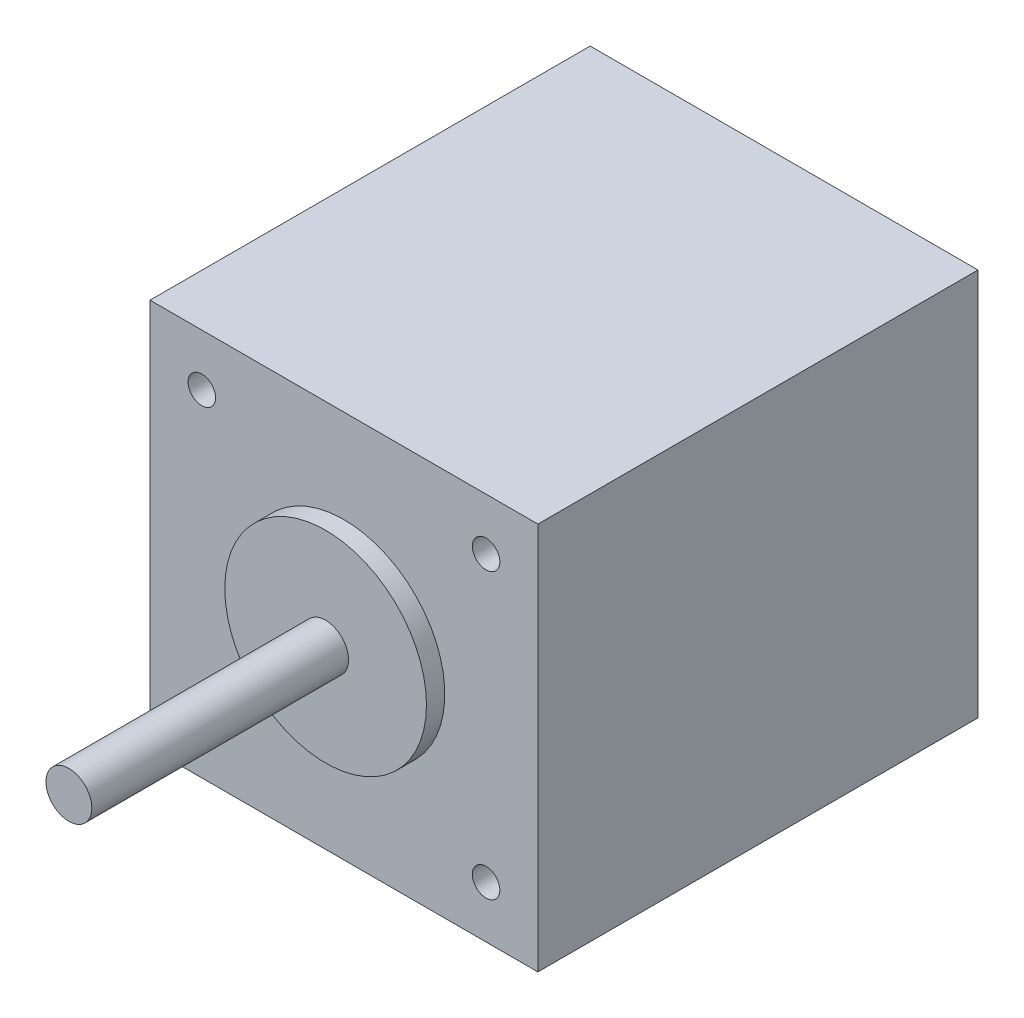
SolidWorks part; units mm, degrees
ref_plane "Спереди" through (0, 0, 0) normal (0, 0, 1) x (1, 0, 0)
ref_plane "Сверху" through (0, 0, 0) normal (0, 1, 0) x (1, 0, 0)
ref_plane "Справа" through (0, 0, 0) normal (1, 0, 0) x (0, 0, -1)
other "Configuration Table"
sketch "Эскиз1" plane through (0, 0, 0) normal (0, 0, 1) x (1, 0, 0)
  line L1 (-21.15, -21.15) -> (21.15, -21.15)
  line L2 (-21.15, -21.15) -> (-21.15, 21.15)
  line L3 (-21.15, 21.15) -> (21.15, 21.15)
  line L4 (21.15, -21.15) -> (21.15, 21.15)
  line L5 (-21.15, -21.15) -> (21.15, 21.15) construction
  line L6 (-21.15, 21.15) -> (21.15, -21.15) construction
  point P0 (0, 0)
  dimension "D1" = 42.3
  dimension "D2" = 42.3
extrude "Корпус" add sketch "Эскиз1" along normal blind 48
sketch "Эскиз2" plane through (0, 0, 0) normal (0, 0, 1) x (1, 0, 0)
  circle A0 centre (0, 0) radius 2.5
extrude "Вал_ПРЕДВ" add sketch "Эскиз2" along normal blind 78
sketch "Эскиз3" plane through (0, 0, 0) normal (0, 0, 1) x (1, 0, 0)
  circle A0 centre (0, 0) radius 11
  dimension "D1" = 22
extrude "Буртик_ПРЕДВ" add sketch "Эскиз3" along normal blind 50
sketch "Эскиз4" plane through (0, 0, 0) normal (0, 0, 1) x (1, 0, 0)
  circle A0 centre (0, 0) radius 8
  dimension "D1" = 16
sketch "Эскиз5" plane through (0, 0, 0) normal (0, 0, 1) x (1, 0, 0)
  circle A0 centre (-15.5, -15.5) radius 1.5
  circle A1 centre (-15.5, 15.5) radius 1.5
  circle A2 centre (15.5, -15.5) radius 1.5
  circle A3 centre (15.5, 15.5) radius 1.5
  dimension "D2" = 3
  dimension "D3" = 3
  dimension "D4" = 3
extrude "Крепеж_М3_ПРЕДВ" cut sketch "Эскиз5" against normal blind 4.5 from offset 48
equation "\"Мотор X ширина корпуса\"= 42.3"
equation "\"Мотор X высота корпуса\"= 42.3"
equation "\"Мотор X длина корпуса\"= 40"
equation "\"Мотор X вылет вала\"= 19.8"
equation "\"Мотор Y ширина корпуса\"= 42.3"
equation "\"Мотор Y высота корпуса\"= 42.3"
equation "\"Мотор Y длина корпуса\"= 48"
equation "\"Мотор Y вылет вала\"= 30"
equation "\"Мотор Z ширина корпуса\"= 42"
equation "\"Мотор Z высота корпуса\"= 42"
equation "\"Мотор Z длина корпуса\"= 40"
equation "\"Мотор Z вылет вала\"= 23"
equation "\"Мотор диаметр вала ПРЕДВ\"= 5"
equation "\"Мотор шаг крепления ПРЕДВ\"= 31"
equation "\"Мотор диаметр отверстий ПРЕДВ\"= 3"
equation "\"Мотор глубина отверстий ПРЕДВ\"= 4.5"
equation "\"Мотор диаметр буртика ПРЕДВ\"= 22"
equation "\"Мотор высота буртика ПРЕДВ\"= 2"
equation "\"Мотор диаметр шкива ПРЕДВ\"= 16"
equation "\"Мотор длина шкива ПРЕДВ\"= 12"
equation "\"Мотор отступ шкива ПРЕДВ\"= 5"
equation "\"Мотор X шаг градусов\"= 1.8"
equation "\"Мотор Y шаг градусов\"= 1.8"
equation "\"Мотор Z шаг градусов\"= 1.8"
equation "\"Мотор Y диаметр ротора\"= 25.78"
equation "\"D1@Эскиз1\" = \"Мотор Y ширина корпуса\""
equation "\"D1@Корпус\" = \"Мотор Y длина корпуса\""
equation "\"D1@Эскиз2\" = \"Мотор диаметр вала ПРЕДВ\""
equation "\"D1@Вал_ПРЕДВ\" = \"Мотор Y длина корпуса\" + \"Мотор Y вылет вала\""
equation "\"D1@Эскиз3\" = \"Мотор диаметр буртика ПРЕДВ\""
equation "\"D1@Буртик_ПРЕДВ\" = \"Мотор Y длина корпуса\" + \"Мотор высота буртика ПРЕДВ\""
equation "\"D1@Эскиз4\" = \"Мотор диаметр шкива ПРЕДВ\""
equation "\"D1@Эскиз5\" = \"Мотор диаметр отверстий ПРЕДВ\""
equation "\"D2@Эскиз5\" = \"Мотор диаметр отверстий ПРЕДВ\""
equation "\"D3@Эскиз5\" = \"Мотор диаметр отверстий ПРЕДВ\""
equation "\"D4@Эскиз5\" = \"Мотор диаметр отверстий ПРЕДВ\""
equation "\"D1@Крепеж_М3_ПРЕДВ\" = \"Мотор глубина отверстий ПРЕДВ\""
equation "\"D19@Крепеж_М3_ПРЕДВ\" = \"Мотор Y длина корпуса\""
equation "\"Ширина груза\"= 160"
equation "\"Глубина груза\"= 240"
equation "\"Высота груза\"= 160"
equation "\"Ширина ячейки\"= \"Ширина груза\" + 10"
equation "\"Глубина ячейки\"= \"Глубина груза\" + 10"
equation "\"Высота ячейки\"= \"Высота груза\" + 10 + 13"
equation "\"Колво ячеек ширина\"= 2"
equation "\"Колво ячеек высота\"= 2"
equation "\"Толщина стенки\" = \"Толщина тонких панелей\""
equation "\"Крепление дверцы\"= 5 "
equation "\"Ширина рейки\"= \"Толщина шестерни\""
equation "\"Высота рейки\"= 20"
equation "\"Высота пола\" = 2*\"Толщина тонких панелей\""
equation "\"Колво полозьев\"= 5"
equation "\"Отступ рейки\"= 20"
equation "\"Глубина каретки\"= \"Глубина ячейки\" + 30 + \"Мотор Y высота корпуса\" + 20 + \"Удлинение платформы по глубине\""
equation "\"Отступ шпильки\"= 26"
equation "\"Диаметр шпильки\"= 5"
equation "\"Длинна шпильки\" = (\"Высота ячейки\"+\"Толщина горизонтальных плит\"+\"Высота пола\")*\"Колво ячеек высота\"+2*(\"Толщина горизонтальных плит\"+\"Отступ рейки\")"
equation "\"Ширина пластины\" = 50"
equation "\"Высота зона выгрузки\"= \"Высота ячейки\" * 2 + \"Толщина стенки\" * 2"
equation "\"Колво выгрузки\"= 1"
equation "\"Отступ крепления мотора фиксации\" = (70-\"Толщина вертикальных стенок\")/2"
equation "\"Ширина ячейки выгрузки\" = \"Ширина ячейки\"+\"Толщина вертикальных стенок\"+2*\"Отступ крепления мотора фиксации\""
equation "\"Длинна рейки\" = (\"Ширина ячейки\"+\"Толщина вертикальных стенок\"+\"Крепление дверцы\")*\"Колво ячеек ширина\"+\"Ширина ячейки выгрузки\"*\"Колво выгрузки\"+\"Толщина вертикальных стенок\"+2*\"Отступ крепления мотора фиксации\"-\"Крепление дверцы\"*\"Колво ячеек ширина\""
equation "\"Толщина шестерни\"= 10"
equation "\"Толщина тонких панелей\" = 6"
equation "\"Толщина вертикальных стенок\" = 6"
equation "\"Толщина горизонтальных плит\" = 6"
equation "\"Базовая высота корпуса\"= (\"Высота ячейки\"+\"Толщина тонких панелей\"+\"Высота пола\")*\"Колво ячеек высота\"+6*\"Толщина тонких панелей\"+\"Мотор X ширина корпуса\"+\"Мотор Y ширина корпуса\"+75"
equation "\"Высота корпуса\"= (\"Высота ячейки\"+\"Толщина горизонтальных плит\"+\"Высота пола\")*\"Колво ячеек высота\"+2*\"Толщина горизонтальных плит\"+4*\"Толщина тонких панелей\"+\"Мотор X ширина корпуса\"+\"Мотор Y ширина корпуса\"+75"
equation "\"Смещение центра корпуса\"= (\"Высота корпуса\"-\"Базовая высота корпуса\")/2-(\"Толщина горизонтальных плит\"-\"Толщина тонких панелей\")"
equation "\"Отметка пола\"= -\"Базовая высота корпуса\"/2+\"Толщина тонких панелей\""
equation "\"Отметка потолка\"= \"Отметка пола\"+\"Высота корпуса\"-2*\"Толщина горизонтальных плит\""
equation "\"Отметка верхней полки\"= \"Отметка потолка\"-(28+\"Толщина тонких панелей\")-\"Высота ячейки\"-\"Высота пола\""
equation "\"Отметка нижней полки\"= \"Отметка верхней полки\"-\"Высота ячейки\"-\"Высота пола\"-\"Толщина горизонтальных плит\""
